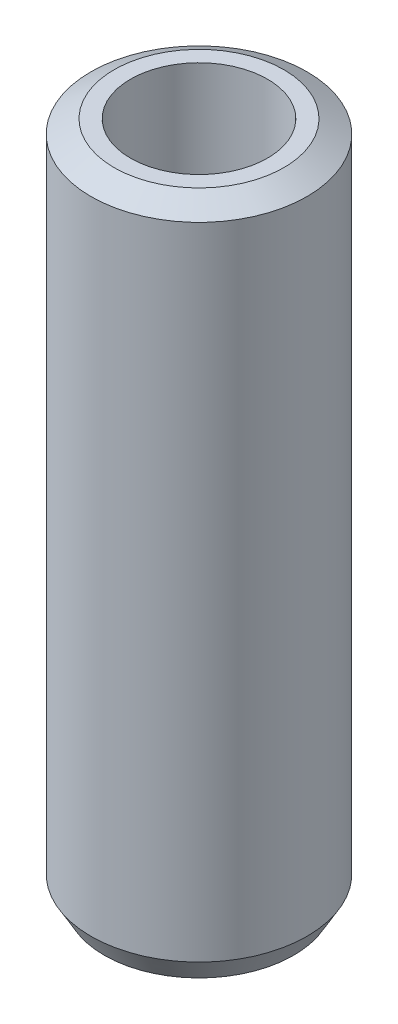
SolidWorks part; units mm, degrees
ref_plane "Front Plane" through (0, 0, 0) normal (0, 0, 1) x (1, 0, 0)
ref_plane "Top Plane" through (0, 0, 0) normal (0, 1, 0) x (1, 0, 0)
ref_plane "Right Plane" through (0, 0, 0) normal (1, 0, 0) x (0, 0, -1)
sketch "Sketch1" plane through (0, 0, 0) normal (0, 1, 0) x (1, 0, 0)
  circle A0 centre (0, 0) radius 22.5
  dimension "SHAFT_OD" = 45
extrude "Boss-Extrude1" add sketch "Sketch1" along normal blind 140.9879
sketch "Sketch2" plane through (0, 0, 0) normal (0, 1, 0) x (1, 0, 0)
  circle A0 centre (0, 0) radius 14.2602
  dimension "BORE_D" = 28.5204
extrude "Cut-Extrude1" cut sketch "Sketch2" along normal through all
chamfer "Chamfer1" distance 2.7887 angle 60 2 edges at (0, 140.9879, 22.5) (0, 0, 22.5) first distance on face at (0, 140.9879, 22.5) first distance on face at (0, 0, 14.2602)
